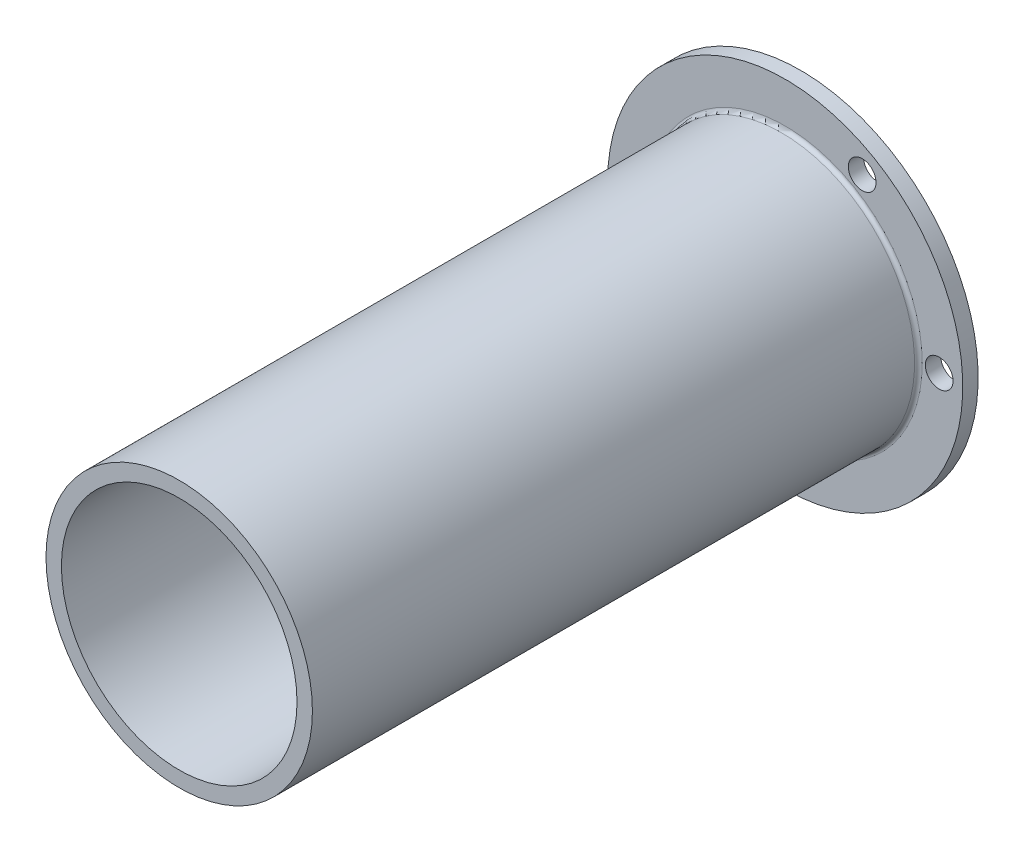
SolidWorks part; units mm, degrees
material "1060 Alloy"
ref_plane "Front Plane" through (0, 0, 0) normal (0, 0, 1) x (1, 0, 0)
ref_plane "Top Plane" through (0, 0, 0) normal (0, 1, 0) x (1, 0, 0)
ref_plane "Right Plane" through (0, 0, 0) normal (1, 0, 0) x (0, 0, -1)
sketch "Sketch1" plane through (0, 0, 0) normal (0, 0, 1) x (1, 0, 0)
  circle A0 centre (0, 0) radius 7.65
  circle A1 centre (0, 0) radius 8.65
  dimension "D1" = 15.3
  dimension "D2" = 17.3
extrude "Boss-Extrude1" add sketch "Sketch1" along normal blind 39.35
sketch "Sketch2" plane through (0, 0, 0) normal (0, 0, -1) x (-1, 0, 0)
  circle A0 centre (0, 0) radius 11.53
  circle A2 centre (0, 0) radius 7.65
  dimension "D1" = 23.06
extrude "Boss-Extrude2" add sketch "Sketch2" along normal blind 1
hole_wizard "M1.6 Clearance Hole1" positions "Sketch10" profile "Sketch11" hole size "M1.6" standard "ISO"
sketch "Sketch10" plane through (0, 0, 0) normal (0, 0, 1) x (1, 0, 0)
  point P0 (-10, 0)
  dimension "D1" = 10
sketch "Sketch11" plane through (-10, 0, 0) normal (1, 0, 0) x (0, -1, 0)
  line L0 (0, 0) -> (0, 5.5408)
  line L1 (0, 5.5408) -> (0.9, 5)
  line L2 (0.9, 5) -> (0.9, 0)
  line L5 (0.9, 0) -> (0, 0)
  line L10 (0, 5.5408) -> (-0.9, 5) construction
  line L11 (0, -6.35) -> (0, 107.95) construction
  dimension "Hole Dia." = 1.8
  dimension "Hole Depth" = 5
  dimension "Drill Angle" = 118
pattern_circular "CirPattern1" count 6 over 360 about axis through (0, 0, 0) along (0, 0, -1) skipping 1, 4 of "M1.6 Clearance Hole1"
fillet "Fillet1" radius 0.25 1 edges at (8.65, 0, 0)
